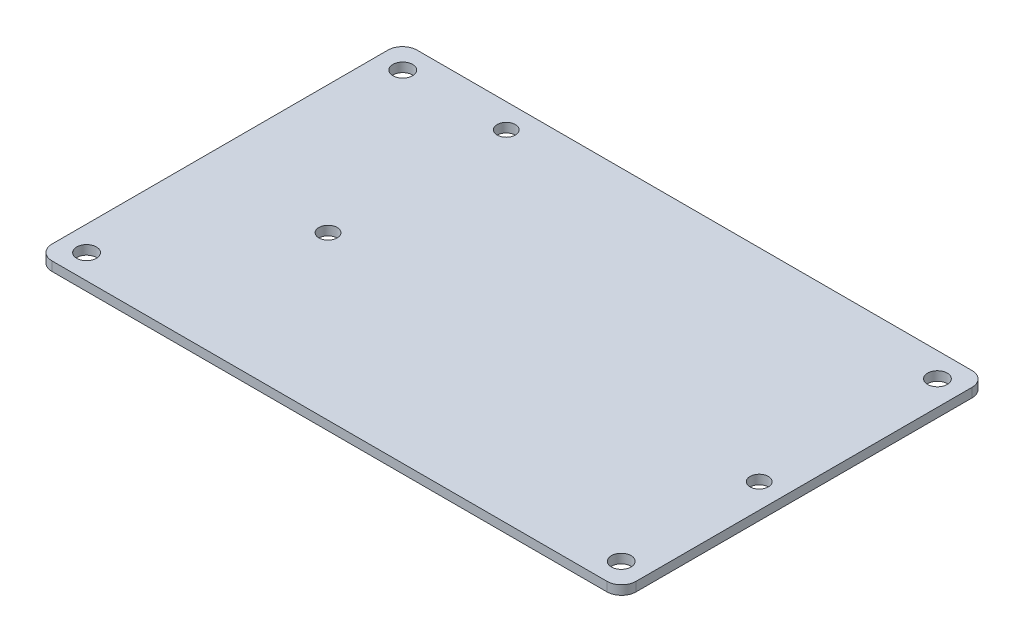
SolidWorks part; units mm, degrees
ref_plane "Front Plane" through (0, 0, 0) normal (0, 0, 1) x (1, 0, 0)
ref_plane "Top Plane" through (0, 0, 0) normal (0, 1, 0) x (1, 0, 0)
ref_plane "Right Plane" through (0, 0, 0) normal (1, 0, 0) x (0, 0, -1)
sketch "Sketch1" plane through (0, 0, 0) normal (0, 1, 0) x (1, 0, 0)
  line L13 (22.3, 59.25) -> (22.3, 28.25) construction
  line L14 (97.3, 28.25) -> (22.3, 28.25) construction
  line L15 (97.3, 59.25) -> (97.3, 28.25) construction
  line L16 (97.3, 59.25) -> (22.3, 59.25) construction
  line L17 (4.3, 59.25) -> (4.3, 4.25) construction
  line L18 (97.3, 4.25) -> (4.3, 4.25) construction
  line L19 (97.3, 59.25) -> (97.3, 4.25) construction
  line L20 (97.3, 59.25) -> (4.3, 59.25) construction
  line L21 (0, 60.96) -> (0, 2.54)
  line L22 (99.06, 0) -> (2.54, 0)
  line L23 (101.6, 60.96) -> (101.6, 2.54)
  line L24 (99.06, 63.5) -> (2.54, 63.5)
  arc A11 (101.6, 2.54) -> (99.06, 0) centre (99.06, 2.54) cw
  arc A12 (2.54, 0) -> (0, 2.54) centre (2.54, 2.54) cw
  arc A13 (2.54, 63.5) -> (0, 60.96) centre (2.54, 60.96) ccw
  arc A14 (99.06, 63.5) -> (101.6, 60.96) centre (99.06, 60.96) cw
  circle A15 centre (22.3, 59.25) radius 1.5875
  circle A16 centre (22.3, 28.25) radius 1.5875
  circle A17 centre (97.3, 28.25) radius 1.5875
  circle A18 centre (97.3, 4.25) radius 1.7145
  circle A19 centre (4.3, 4.25) radius 1.7145
  circle A20 centre (4.3, 59.25) radius 1.7145
  circle A21 centre (97.3, 59.25) radius 1.7145
  point P62 (101.8108, 0.0462)
  point P63 (0.2108, 0.0462)
  point P64 (101.8108, 63.5462)
  point P65 (50.8, 63.5)
  point P66 (101.6, 31.75)
  point P67 (97.3, 31.75)
  point P68 (50.8, 59.25)
  dimension "D1" = 3.429
  dimension "D6" = 55
  dimension "D9" = 31
  dimension "D2" = 3.175
  dimension "D7" = 2.54
  dimension "D3" = 63.5
  dimension "D4" = 101.6
  dimension "D5" = 93
  dimension "D8" = 75
extrude "Boss-Extrude1" add sketch "Sketch1" along normal blind 1.6
